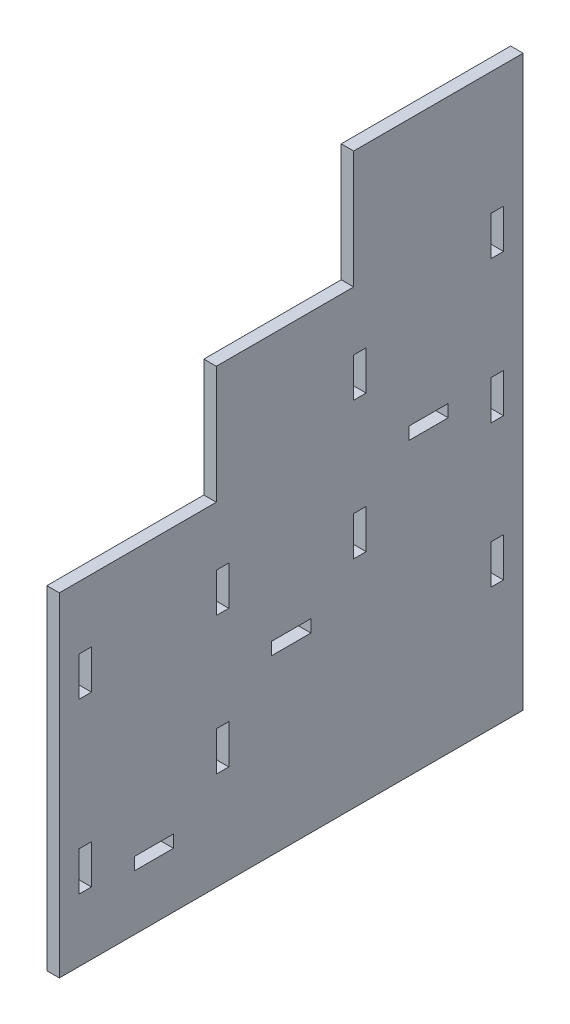
SolidWorks part; units mm, degrees
ref_plane "Alzado" through (0, 0, 0) normal (0, 0, 1) x (1, 0, 0)
ref_plane "Planta" through (0, 0, 0) normal (0, 1, 0) x (1, 0, 0)
ref_plane "Vista lateral" through (0, 0, 0) normal (1, 0, 0) x (0, 0, -1)
sketch "Croquis1" plane through (0, 0, 0) normal (1, 0, 0) x (0, 0, -1)
  line L0 (-117.243, -155.2025) -> (-117.243, 14.7975)
  line L1 (-117.243, 14.7975) -> (-47.243, 14.7975)
  line L2 (-47.243, 14.7975) -> (-47.243, 74.7975)
  line L3 (-47.243, 74.7975) -> (22.757, 74.7975)
  line L4 (22.757, 74.7975) -> (22.757, 134.7975)
  line L5 (22.757, 134.7975) -> (92.757, 134.7975)
  line L6 (92.757, 134.7975) -> (92.757, -155.2025)
  line L7 (92.757, -155.2025) -> (-117.243, -155.2025)
extrude "Saliente-Extruir1" add sketch "Croquis1" along normal blind 6.35
sketch "Croquis2" plane through (0, 0, 0) normal (-1, 0, 0) x (0, 0, 1)
  line L0 (117.243, 14.7975) -> (117.243, -155.2025) construction
  line L1 (117.243, -17.2025) -> (110.893, -17.2025)
  line L2 (117.243, -17.2025) -> (117.243, -37.2025)
  line L3 (117.243, -37.2025) -> (110.893, -37.2025)
  line L4 (110.893, -17.2025) -> (110.893, -37.2025)
  line L5 (47.243, 14.7975) -> (117.243, 14.7975) construction
  line L6 (117.243, -70.2025) -> (-92.757, -70.2025) construction
  line L7 (-92.757, -155.2025) -> (-92.757, 134.7975) construction
  line L8 (110.893, -123.2025) -> (110.893, -103.2025)
  line L9 (117.243, -103.2025) -> (110.893, -103.2025)
  line L10 (117.243, -123.2025) -> (117.243, -103.2025)
  line L11 (117.243, -123.2025) -> (110.893, -123.2025)
  line L12 (-22.757, 74.7975) -> (-22.757, -135.2025) construction
  line L13 (117.243, -155.2025) -> (-92.757, -155.2025) construction
  line L14 (47.243, 14.7975) -> (47.243, -135.2025) construction
  line L15 (117.243, -135.2025) -> (-92.757, -135.2025) construction
  line L16 (-92.757, -128.8525) -> (117.243, -128.8525) construction
  line L17 (47.243, -60.2025) -> (-92.757, -60.2025) construction
  line L18 (47.243, -15.2025) -> (40.893, -15.2025)
  line L19 (47.243, -15.2025) -> (47.243, -35.2025)
  line L20 (47.243, -35.2025) -> (40.893, -35.2025)
  line L21 (40.893, -15.2025) -> (40.893, -35.2025)
  line L22 (40.893, -105.2025) -> (40.893, -85.2025)
  line L23 (47.243, -85.2025) -> (40.893, -85.2025)
  line L24 (47.243, -105.2025) -> (47.243, -85.2025)
  line L25 (47.243, -105.2025) -> (40.893, -105.2025)
  line L26 (-22.757, 74.7975) -> (47.243, 74.7975) construction
  line L27 (-22.757, 44.7975) -> (-29.107, 44.7975)
  line L28 (-22.757, 44.7975) -> (-22.757, 24.7975)
  line L29 (-22.757, 24.7975) -> (-29.107, 24.7975)
  line L30 (-29.107, 44.7975) -> (-29.107, 24.7975)
  line L32 (-22.757, -25.2025) -> (-29.107, -25.2025)
  line L33 (-22.757, -25.2025) -> (-22.757, -45.2025)
  line L34 (-22.757, -45.2025) -> (-29.107, -45.2025)
  line L35 (-29.107, -25.2025) -> (-29.107, -45.2025)
  dimension "D1" = 6.35
  dimension "D2" = 20
  dimension "D3" = 32
  dimension "D4" = 20
  dimension "D5" = 6.35
  dimension "D6" = 30
  dimension "D7" = 30
  dimension "D8" = 50
extrude "Cortar-Extruir1" cut sketch "Croquis2" against normal blind 10
sketch "Croquis3" plane through (0, 0, 0) normal (1, 0, 0) x (0, 0, -1)
  line L0 (-117.243, -155.2025) -> (92.757, -155.2025) construction
  line L1 (92.757, 134.7975) -> (99.107, 134.7975)
  line L2 (92.757, 134.7975) -> (92.757, -155.2025)
  line L3 (92.757, -155.2025) -> (99.107, -155.2025)
  line L4 (99.107, 134.7975) -> (99.107, -155.2025)
  dimension "D1" = 6.35
extrude "Saliente-Extruir2" add sketch "Croquis3" along normal blind 6.35
sketch "Croquis4" plane through (0, 0, 0) normal (-1, 0, 0) x (0, 0, 1)
  line L0 (-99.107, -0.2025) -> (-92.757, -0.2025)
  line L1 (-99.107, -155.2025) -> (-99.107, 134.7975) construction
  line L2 (-99.107, 52.2975) -> (-92.757, 52.2975)
  line L3 (-99.107, 52.2975) -> (-99.107, 72.2975)
  line L4 (-99.107, 72.2975) -> (-92.757, 72.2975)
  line L5 (-92.757, 52.2975) -> (-92.757, 72.2975)
  line L6 (-99.107, 52.2975) -> (-92.757, 72.2975) construction
  line L7 (-99.107, 72.2975) -> (-92.757, 52.2975) construction
  line L8 (-99.107, 134.7975) -> (-22.757, 134.7975) construction
  line L9 (-99.107, -0.2025) -> (-99.107, -20.2025)
  line L10 (-99.107, -20.2025) -> (-92.757, -20.2025)
  line L11 (-92.757, -0.2025) -> (-92.757, -20.2025)
  line L12 (-99.107, -0.2025) -> (-92.757, -20.2025) construction
  line L13 (-99.107, -20.2025) -> (-92.757, -0.2025) construction
  line L14 (-99.107, -72.7025) -> (-92.757, -72.7025)
  line L15 (-99.107, -72.7025) -> (-99.107, -92.7025)
  line L16 (-99.107, -92.7025) -> (-92.757, -92.7025)
  line L17 (-92.757, -72.7025) -> (-92.757, -92.7025)
  line L18 (-99.107, -72.7025) -> (-92.757, -92.7025) construction
  line L19 (-99.107, -92.7025) -> (-92.757, -72.7025) construction
  line L20 (117.243, -155.2025) -> (-99.107, -155.2025) construction
  point P2 (-95.932, 62.2975)
  point P9 (-95.932, -10.2025)
  point P14 (-95.932, -82.7025)
  dimension "D1" = 20
  dimension "D2" = 6.35
  dimension "D3" = 72.5
  dimension "D4" = 72.5
  dimension "D5" = 72.5
  dimension "D6" = 72.5
extrude "Cortar-Extruir2" cut sketch "Croquis4" against normal blind 6.35
sketch "Croquis5" plane through (6.35, 0, 0) normal (1, 0, 0) x (0, 0, -1)
  line L0 (-117.243, -155.2025) -> (99.107, -155.2025) construction
  line L1 (-89.063, -120.6925) -> (-69.063, -120.6925)
  line L2 (-89.063, -120.6925) -> (-89.063, -127.0425)
  line L3 (-89.063, -127.0425) -> (-69.063, -127.0425)
  line L4 (-69.063, -120.6925) -> (-69.063, -127.0425)
  line L5 (-19.063, -60.6925) -> (0.937, -60.6925)
  line L6 (-19.063, -60.6925) -> (-19.063, -67.0425)
  line L7 (-19.063, -67.0425) -> (0.937, -67.0425)
  line L8 (0.937, -60.6925) -> (0.937, -67.0425)
  line L9 (50.937, -0.6925) -> (70.937, -0.6925)
  line L10 (50.937, -0.6925) -> (50.937, -7.0425)
  line L11 (50.937, -7.0425) -> (70.937, -7.0425)
  line L12 (70.937, -0.6925) -> (70.937, -7.0425)
  line L13 (-117.243, -123.2025) -> (-117.243, -155.2025) construction
  point P12 (0, 0)
  point P17 (60.937, -7.0425)
  dimension "D1" = 20
  dimension "D2" = 6.35
  dimension "D3" = 28.16
  dimension "D4" = 28.18
  dimension "D5" = 60
  dimension "D6" = 50
  dimension "D7" = 60
  dimension "D8" = 50
extrude "Cortar-Extruir3" cut sketch "Croquis5" against normal blind 10
sketch "Croquis6" plane through (0, 0, 0) normal (1, 0, 0) x (0, 0, -1)
  line L0 (-117.243, -155.2025) -> (99.107, -155.2025) construction
  line L1 (99.107, 134.7975) -> (109.107, 134.7975)
  line L2 (99.107, 134.7975) -> (99.107, -155.2025)
  line L3 (99.107, -155.2025) -> (109.107, -155.2025)
  line L4 (109.107, 134.7975) -> (109.107, -155.2025)
  line L5 (-117.243, 14.7975) -> (-127.243, 14.7975)
  line L6 (-117.243, 14.7975) -> (-117.243, -155.2025)
  line L7 (-117.243, -155.2025) -> (-127.243, -155.2025)
  line L8 (-127.243, 14.7975) -> (-127.243, -155.2025)
  dimension "D1" = 10
extrude "Saliente-Extruir3" add sketch "Croquis6" along normal up to surface (6.35 mm away) up to face at (6.35, -123.8675, 79.063)
